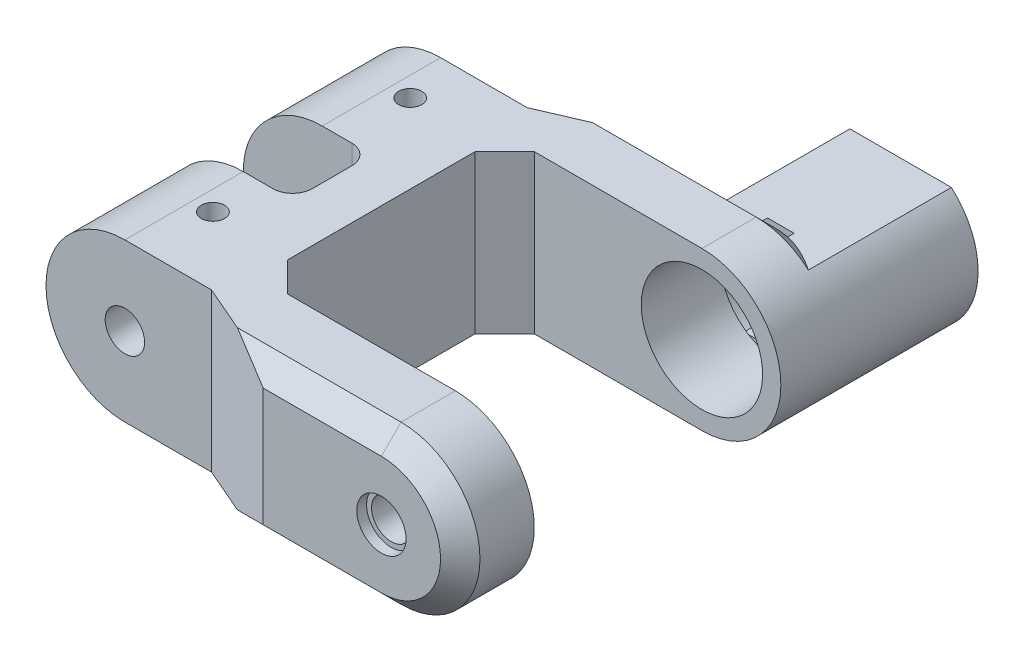
SolidWorks part; units mm, degrees
ref_plane "Alzado" through (0, 0, 0) normal (0, 0, 1) x (1, 0, 0)
ref_plane "Planta" through (0, 0, 0) normal (0, 1, 0) x (1, 0, 0)
ref_plane "Vista lateral" through (0, 0, 0) normal (1, 0, 0) x (0, 0, -1)
sketch "Croquis1" plane through (0, 0, 0) normal (0, 0, 1) x (1, 0, 0)
  line L0 (0, 0) -> (20379.0667, 0) construction
  line L1 (0, 0) -> (0, 20379.0667) construction
  line L2 (0, 8) -> (30, 8)
  line L3 (0, -8) -> (30, -8)
  arc A0 (0, 8) -> (0, -8) centre (0, 0) ccw
  arc A1 (30, 8) -> (30, -8) centre (30, 0) cw
  circle A2 centre (0, 0) radius 2
  circle A3 centre (30, 0) radius 2
  dimension "D1" = 8
  dimension "D2" = 4
  dimension "D3" = 4
  dimension "D4" = 30
extrude "Saliente-Extruir1" add sketch "Croquis1" along normal mid plane 40
sketch "Croquis2" plane through (0, 0, 0) normal (0, 1, 0) x (1, 0, 0)
  line L0 (0, 0) -> (50000, 0) construction
  line L1 (-8, 16) -> (8.7746, 16)
  line L2 (-8, 20) -> (-8, -20) construction
  line L3 (8.7746, 16) -> (18.0245, 20)
  line L4 (30, 20) -> (0, 20) construction
  line L5 (18.0245, 20) -> (-8, 20)
  line L6 (-8, 20) -> (-8, 16)
  dimension "D1" = 32
extrude "Cortar-Extruir1" cut sketch "Croquis2" against normal through all both and the other way through all
mirror "Simetría1" about plane through (0, 0, 0) normal (0, 0, 1) of "Cortar-Extruir1"
sketch "Croquis3" plane through (0, 0, 0) normal (0, 1, 0) x (1, 0, 0)
  line L0 (30, -20) -> (30, 20) construction
  line L1 (50, -12.5) -> (10, -12.5)
  line L2 (50, -12.5) -> (50, 12.5)
  line L3 (50, 12.5) -> (10, 12.5)
  line L4 (10, -12.5) -> (10, 12.5)
  line L5 (50, -12.5) -> (10, 12.5) construction
  line L6 (50, 12.5) -> (10, -12.5) construction
  point P0 (30, 0)
  dimension "D1" = 25
  dimension "D2" = 40
extrude "Cortar-Extruir2" cut sketch "Croquis3" against normal through all both and the other way through all
sketch "Sketch8" plane through (0, 0, 0) normal (0, 0, 1) x (1, 0, 0)
  line L10 (-1.0301, -1.7143) -> (-7.9181, -13.1779)
  line L18 (-6.7894, -13.8561) -> (0, -8)
  line L20 (0, -2) -> (0, -8)
  line L23 (-7.9181, -13.1779) -> (-6.7894, -13.8561)
  circle A1 centre (0, 0) radius 2 construction
  circle A2 centre (0, 0) radius 2
extrude "Boss-Extrude2" add sketch "Sketch8" along normal blind 5 from surface contours L20 L10 L18 | L20 L18 L10 region at (-3.0583, -7.9478, 0) starting at face at (2, 0, -16)
chamfer "Chaflán1" distance 2 angle 45 6 edges at (24.0122, -8, -20) (38, 0, -20) (24.0122, 8, -20) (24.0122, -8, 20) (38, 0, 20) (24.0122, 8, 20)
chamfer "Chaflán2" distance 3 angle 45 2 edges at (10, 0, -12.5) (10, 0, 12.5)
sketch "Croquis4" plane through (0, 0, 0) normal (0, 1, 0) x (1, 0, 0)
  line L0 (0, 0) -> (-50000, 0) construction
  line L2 (5, -4) -> (-8, -4)
  line L3 (5, -4) -> (5, 4)
  line L4 (5, 4) -> (-8, 4)
  line L5 (-8, -4) -> (-8, 4)
  line L6 (5, -4) -> (-8, 4) construction
  line L7 (5, 4) -> (-8, -4) construction
  line L8 (0, 16) -> (-8, 16) construction
  line L9 (0, -16) -> (0, 16) construction
  line L10 (-8, 16) -> (-8, -16) construction
  point P3 (-1.5, 0)
  dimension "D1" = 12
  dimension "D2" = 5
extrude "Cortar-Extruir3" cut sketch "Croquis4" against normal through all both and the other way through all
sketch "Sketch4" plane through (0, 0, 0) normal (0, 0, 1) x (1, 0, 0)
  line L0 (22, 6) -> (22, -6)
  line L4 (30, 6) -> (18.0245, 6) construction
  line L5 (22, -6) -> (35.2915, -6)
  line L7 (30, 0) -> (30, 6) construction
  line L10 (35.2915, 6) -> (22, 6)
  circle A3 centre (30, 0) radius 2
  circle A4 centre (30, 0) radius 2 construction
  arc A5 (30, -8) -> (30, 8) centre (30, 0) ccw construction
  arc A6 (35.2915, -6) -> (35.2915, 6) centre (30, 0) ccw
  dimension "D1" = 8
extrude "Boss-Extrude1" add sketch "Sketch4" against normal blind 20 from surface starting at face at (28, 0, -12.5)
sketch "Sketch6" plane through (0, 0, 0) normal (0, 0, 1) x (1, 0, 0)
  line L1 (36.1, 5.1) -> (23.9, 5.1) construction
  line L2 (36.1, 5.1) -> (36.1, -5.1) construction
  line L3 (36.1, -5.1) -> (23.9, -5.1) construction
  line L4 (23.9, 5.1) -> (23.9, -5.1) construction
  line L5 (36.1, 5.1) -> (23.9, -5.1) construction
  line L6 (36.1, -5.1) -> (23.9, 5.1) construction
  circle A0 centre (30, 0) radius 6.15
  dimension "D1" = 12.3
  dimension "D2" = 10.2
  dimension "D3" = 12.2
extrude "Cut-Extrude2" cut sketch "Sketch6" against normal blind 8 from surface starting at face at (23.5, 0, -12.5)
sketch "Sketch5" plane through (0, 0, 0) normal (0, 0, 1) x (1, 0, 0)
  line L0 (30, 0) -> (41.8422, 0) construction
  line L1 (26.269, 5.2) -> (33.731, 5.2)
  line L2 (26.269, -5.2) -> (33.731, -5.2)
  arc A0 (26.269, 5.2) -> (26.269, -5.2) centre (30, 0) ccw
  arc A1 (33.731, -5.2) -> (33.731, 5.2) centre (30, 0) ccw
  dimension "D1" = 12.8
  dimension "D2" = 5.2
extrude "Cut-Extrude1" cut sketch "Sketch5" against normal through all from surface starting at face at (28, 0, -20.5)
sketch "Sketch7" plane through (0, 0, 0) normal (0, 0, 1) x (1, 0, 0)
  circle A0 centre (30, 0) radius 2.5
  dimension "D1" = 5
extrude "Cut-Extrude3" cut sketch "Sketch7" against normal blind 1 from surface starting at face at (32, 0, 20)
chamfer "Chamfer2" distance 3 angle 45 2 edges at (22, -6, -26.25) (22, 6, -26.25)
sketch "Sketch9" plane through (0, 0, 0) normal (0, 1, 0) x (1, 0, 0)
  line L1 (0.825, 10.9232) -> (1.825, 10.9232) construction
  line L2 (0, 16) -> (-8, 16) construction
  line L4 (0, -16) -> (0, 29.1951) construction
  circle A0 centre (2, 10.9232) radius 1.175
  circle A1 centre (2, -9.0768) radius 1.175
  circle A3 centre (0, 10.5732) radius 2 construction
  dimension "D1" = 2.35
  dimension "D3" = 4
  dimension "D5" = 20
  dimension "D2" = 5.0768
  dimension "D4" = 1
extrude "Cut-Extrude4" cut sketch "Sketch9" along normal through all and the other way through all
fillet "Fillet1" radius 2 2 edges at (5, 0, 4) (5, 0, -4)
